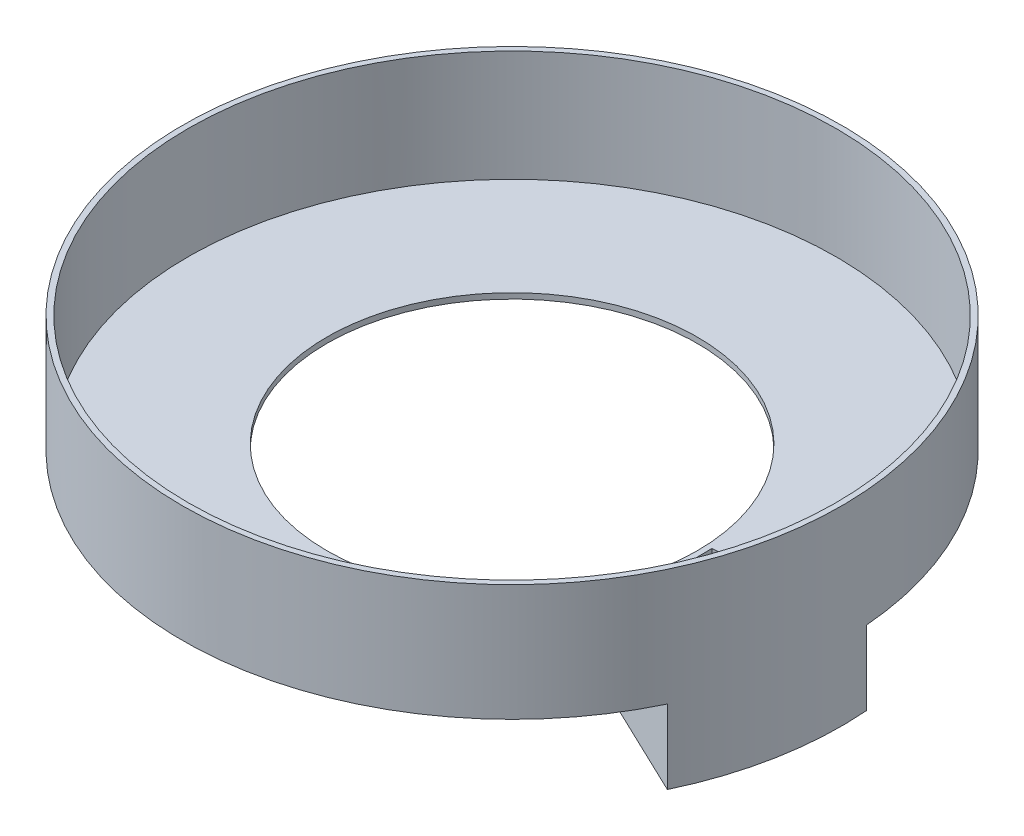
SolidWorks part; units mm, degrees
ref_plane "Front Plane" through (0, 0, 0) normal (0, 0, 1) x (1, 0, 0)
ref_plane "Top Plane" through (0, 0, 0) normal (0, 1, 0) x (1, 0, 0)
ref_plane "Right Plane" through (0, 0, 0) normal (1, 0, 0) x (0, 0, -1)
sketch "Sketch2" plane through (0, 0, 0) normal (0, 1, 0) x (1, 0, 0)
  circle A1 centre (0, 0) radius 178
  circle A2 centre (0, 0) radius 100
extrude "Boss-Extrude1" add sketch "Sketch2" along normal blind 3
sketch "Sketch3" plane through (0, 3, 0) normal (0, 1, 0) x (1, 0, 0)
  circle A0 centre (0, 0) radius 175
  circle A1 centre (0, 0) radius 178
  dimension "D1" = 3
extrude "Boss-Extrude2" add sketch "Sketch3" along normal blind 60
sketch "Sketch5" plane through (0, 3, 0) normal (0, 1, 0) x (1, 0, 0)
  line L0 (0, 0) -> (174.4708, 13.5988)
  line L1 (0, 0) -> (157.8956, -75.4585)
  line L2 (174.4708, 13.5988) -> (45.5792, 75.1963)
  circle A1 centre (0, 0) radius 175 construction
  arc A2 (99.6976, 7.7707) -> (90.226, -43.1191) centre (0, 0) cw
  circle A3 centre (0, 0) radius 100 construction
  arc A4 (174.4708, 13.5988) -> (157.8956, -75.4585) centre (0, 0) cw
  circle M3 centre (0, 0) radius 100
  circle M4 centre (0, 0) radius 175
  dimension "D1" = 30
  dimension "D2" = 30
extrude "Cut-Extrude2" cut sketch "Sketch5" against normal blind 25 contours L1 L0 M3 M4 region at (136.9531, 3, 25.4896)
ref_plane "Plane2" through (0, 30, 0) normal (0, 1, 0) x (1, 0, 0)
sketch "Sketch16" plane through (0, 0, 0) normal (0, -1, 0) x (1, 0, 0)
  line L0 (99.6976, -7.7707) -> (174.4708, -13.5988) construction
  line L1 (90.226, 43.1191) -> (157.8956, 75.4585) construction
  line L2 (99.6976, -7.7707) -> (174.4708, -13.5988) construction
  line L3 (90.226, 43.1191) -> (157.8956, 75.4585) construction
  line L4 (160.6024, 76.7521) -> (90.226, 43.1191)
  line L5 (99.6976, -7.7707) -> (177.4618, -13.8319)
  line L6 (159.1659, 72.7406) -> (94.187, 41.6871)
  line L7 (102.8781, -5.0095) -> (174.6783, -10.6059)
  arc A0 (174.4708, -13.5988) -> (157.8956, 75.4585) centre (0, 0) ccw construction
  arc A1 (174.4708, -13.5988) -> (157.8956, 75.4585) centre (0, 0) ccw construction
  arc A2 (90.226, 43.1191) -> (99.6976, -7.7707) centre (0, 0) cw
  arc A3 (160.6024, 76.7521) -> (177.4618, -13.8319) centre (0, 0) cw
  circle A4 centre (0, 0) radius 178 construction
  arc A5 (94.187, 41.6871) -> (102.8781, -5.0095) centre (0, 0) cw
  arc A6 (159.1659, 72.7406) -> (174.6783, -10.6059) centre (0, 0) cw
  dimension "D1" = 3
extrude "Boss-Extrude17" add sketch "Sketch16" along normal blind 40 and the other way blind 3
